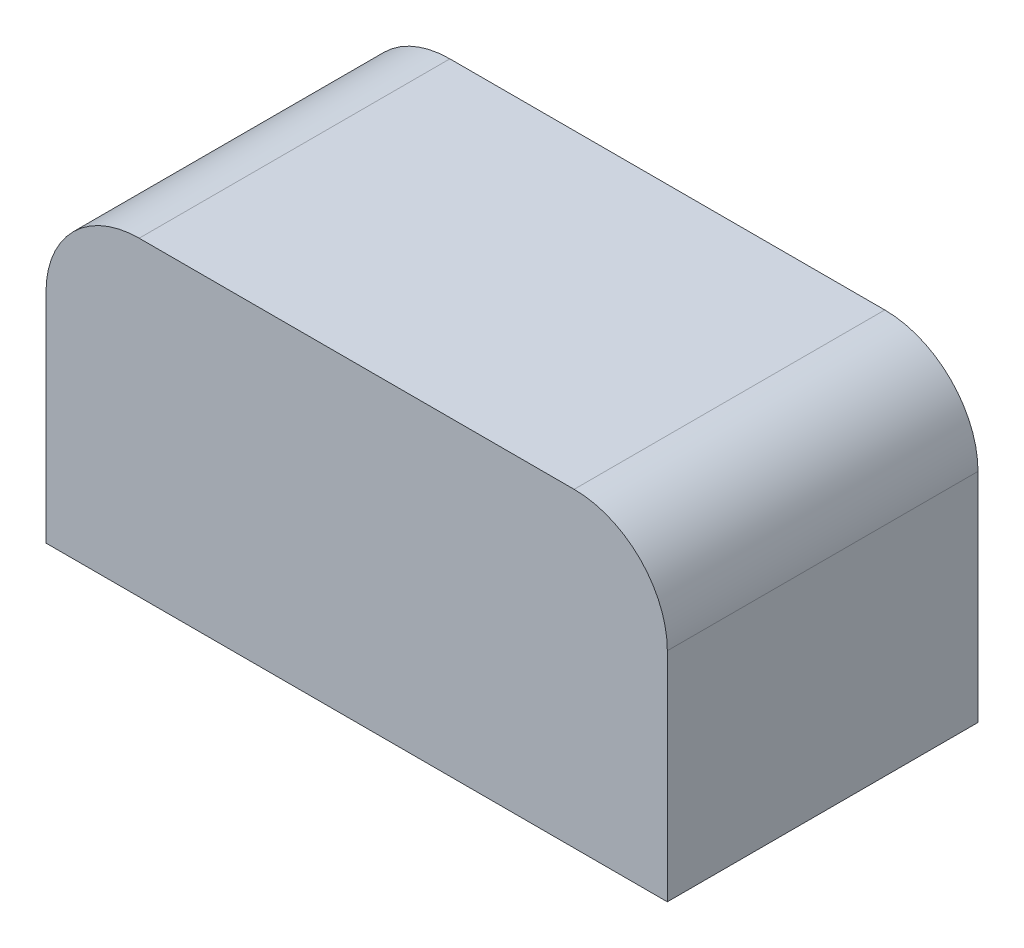
SolidWorks part; units mm, degrees
ref_plane "Front Plane" through (0, 0, 0) normal (0, 0, 1) x (1, 0, 0)
ref_plane "Top Plane" through (0, 0, 0) normal (0, 1, 0) x (1, 0, 0)
ref_plane "Right Plane" through (0, 0, 0) normal (1, 0, 0) x (0, 0, -1)
sketch "Sketch1" plane through (0, 0, 0) normal (0, 0, 1) x (1, 0, 0)
  line L0 (-165.3614, 249.3811) -> (-159.1604, 249.3811) construction
  line L1 (-173.0217, 239.3811) -> (-153.0217, 239.3811)
  line L2 (-173.0217, 239.3811) -> (-173.0217, 249.3811)
  line L3 (-173.0217, 249.3811) -> (-153.0217, 249.3811)
  line L4 (-153.0217, 239.3811) -> (-153.0217, 249.3811)
  spline S0 degree 3 poles (-162.2682, 252.2954) (-160.185, 251.5588) (-160.5587, 249.3811) (-162.7682, 249.3811) (-164.9777, 249.3811) (-165.3514, 251.5588) (-163.2682, 252.2954) knots 0 0 0 0 0.5 0.5 0.5 1 1 1 1 weights 1 0.446068 0.446068 1 0.446068 0.446068 1 construction
  dimension "D1" = 10
  dimension "D2" = 0
  dimension "D3" = 20
extrude "Boss-Extrude1" add sketch "Sketch1" along normal blind 10
fillet "Fillet1" radius 3 2 edges at (-153.0217, 249.3811, 5) (-173.0217, 249.3811, 5)
